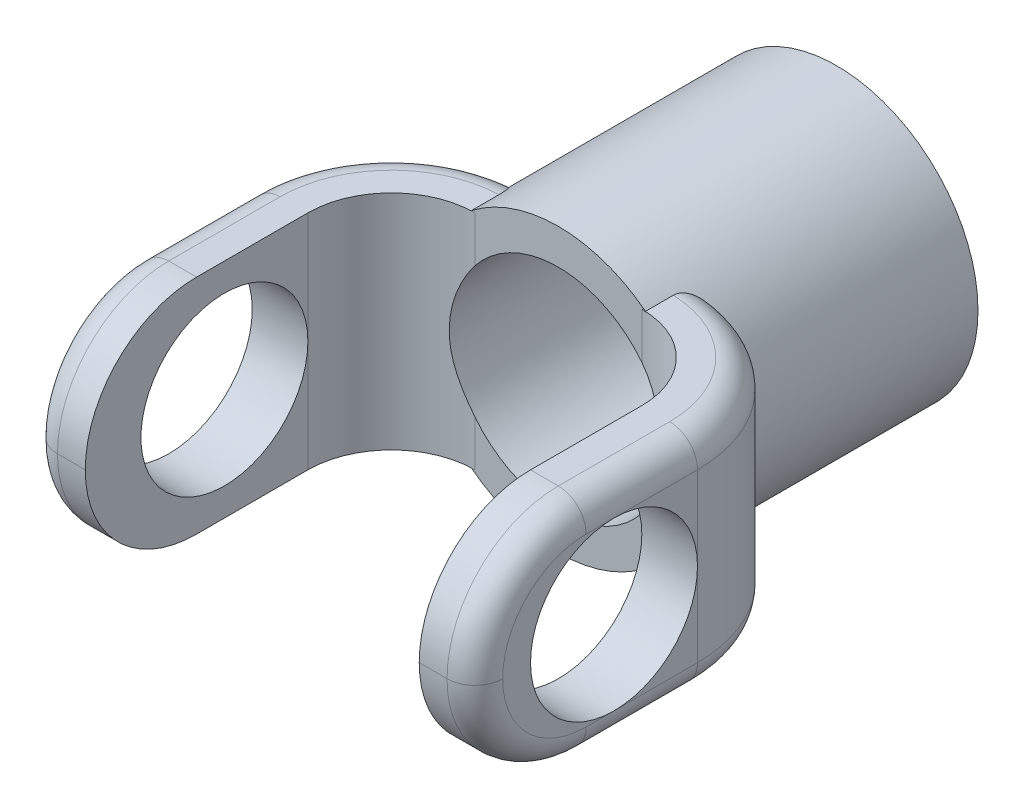
SolidWorks part; units mm, degrees
material "Alloy Steel"
ref_plane "Front Plane" through (0, 0, 0) normal (0, 0, 1) x (1, 0, 0)
ref_plane "Top Plane" through (0, 0, 0) normal (0, 1, 0) x (1, 0, 0)
ref_plane "Right Plane" through (0, 0, 0) normal (1, 0, 0) x (0, 0, -1)
sketch "Sketch1" plane through (0, 0, 0) normal (0, 1, 0) x (1, 0, 0)
  line L0 (-20, 0) -> (20, 0)
  line L1 (20, -7.5) -> (20, 7.5)
  line L2 (15, -7.5) -> (15, 7.5)
  line L3 (0, -20) -> (0, 20) construction
  line L4 (15, -7.5) -> (20, -7.5) construction
  line L5 (15, -7.5) -> (15, -12.5)
  line L6 (15, -12.5) -> (20, -12.5)
  line L7 (20, -7.5) -> (20, -12.5)
  line L8 (-20, -7.5) -> (-20, -12.5)
  line L9 (-15, -7.5) -> (-15, -12.5)
  line L10 (-15, -12.5) -> (-20, -12.5)
  line L11 (-20, -7.5) -> (-20, 7.5)
  line L12 (-15, -7.5) -> (-15, 7.5)
  line L13 (12.5, -7.5) -> (12.5, 7.5)
  line L14 (-7.5, 12.5) -> (7.5, 12.5)
  line L15 (-7.5, 15) -> (7.5, 15)
  line L16 (-7.5, 20) -> (7.5, 20)
  circle A0 centre (0, 0) radius 7.5
  arc A1 (12.5, 7.5) -> (7.5, 12.5) centre (7.5, 7.5) ccw
  arc A2 (15, 7.5) -> (7.5, 15) centre (7.5, 7.5) ccw
  arc A3 (-15, 7.5) -> (-7.5, 15) centre (-7.5, 7.5) cw
  arc A4 (7.5, 20) -> (20, 7.5) centre (7.5, 7.5) cw
  arc A5 (-7.5, 20) -> (-20, 7.5) centre (-7.5, 7.5) ccw
  point P4 (0, 0)
  point P8 (20, 0)
  point P11 (15, 0)
  point P15 (0, 0)
  point P23 (7.5, 0)
  point P26 (12.5, 0)
  point P27 (0, 7.5)
  point P31 (0, 12.5)
  point P32 (12.5, 12.5)
  point P37 (0, 15)
  point P41 (0, 20)
  point P42 (0, 0)
  dimension "D6" = 15
  dimension "D9" = 5
  dimension "D1" = 40
  dimension "D2" = 15
  dimension "D3" = 5
  dimension "D4" = 5
  dimension "D5" = 40
  dimension "D7" = 5
  dimension "D8" = 5
extrude "Boss-Extrude1" add sketch "Sketch1" along normal mid plane 20 contours L16 A5 L11 L0 L12 A3 L15 A2 L2 L1 A4 | L9 L12 L0 L11 L8 L10 | L7 L1 L0 L2 L5 L6 region at (-19.5528, 0, -3.75) region at (-17.5, 0, 6.25) region at (17.5, 0, 6.25)
sketch "Sketch2" plane through (20, 0, 0) normal (1, 0, 0) x (0, 0, -1)
  circle A0 centre (0, 0) radius 7.5
  dimension "D1" = 15
extrude "Cut-Extrude1" cut sketch "Sketch2" against normal through all both and the other way through all
sketch "Sketch3" plane through (0, 0, -20) normal (0, 0, -1) x (-1, 0, 0)
  circle A0 centre (0, 0) radius 9.525
  circle A1 centre (0, 0) radius 12.7
  line M3 (7.5, -10) -> (7.5, 10)
  line M5 (-7.5, 10) -> (-7.5, -10)
  dimension "D1" = 19.05
  dimension "D2" = 25.4
extrude "Boss-Extrude2" add sketch "Sketch3" along normal blind 20 and the other way up to surface (5 mm away) other way up to face at (0, 0, -15)
extrude "Cut-Extrude2" cut sketch "Sketch3<2>" against normal through all both contours A0 M3 M5 | A0 M5 | A0 M3 region at (-8.3179, 0, -20) region at (0, 0, -20) region at (8.3179, 0, -20)
sketch "Sketch3<2>" plane through (0, 0, -20) normal (0, 0, -1) x (-1, 0, 0) same geometry as "Sketch3"
fillet "Fillet1" radius 10 4 edges at (-17.5, -10, 12.5) (-17.5, 10, 12.5) (17.5, -10, 12.5) (17.5, 10, 12.5)
fillet "Fillet2" radius 2.5 12 edges at (-16.4543, -10, -16.2218) (-20, -10, -2.5) (-20, -7.0711, 9.5711) (-16.4543, 10, -16.2218) (-20, 10, -2.5) (16.4543, -10, -16.2218) (20, -10, -2.5) (20, -7.0711, 9.5711) (20, 7.0711, 9.5711) (20, 10, -2.5) (-20, 7.0711, 9.5711) (16.4543, 10, -16.2218)
